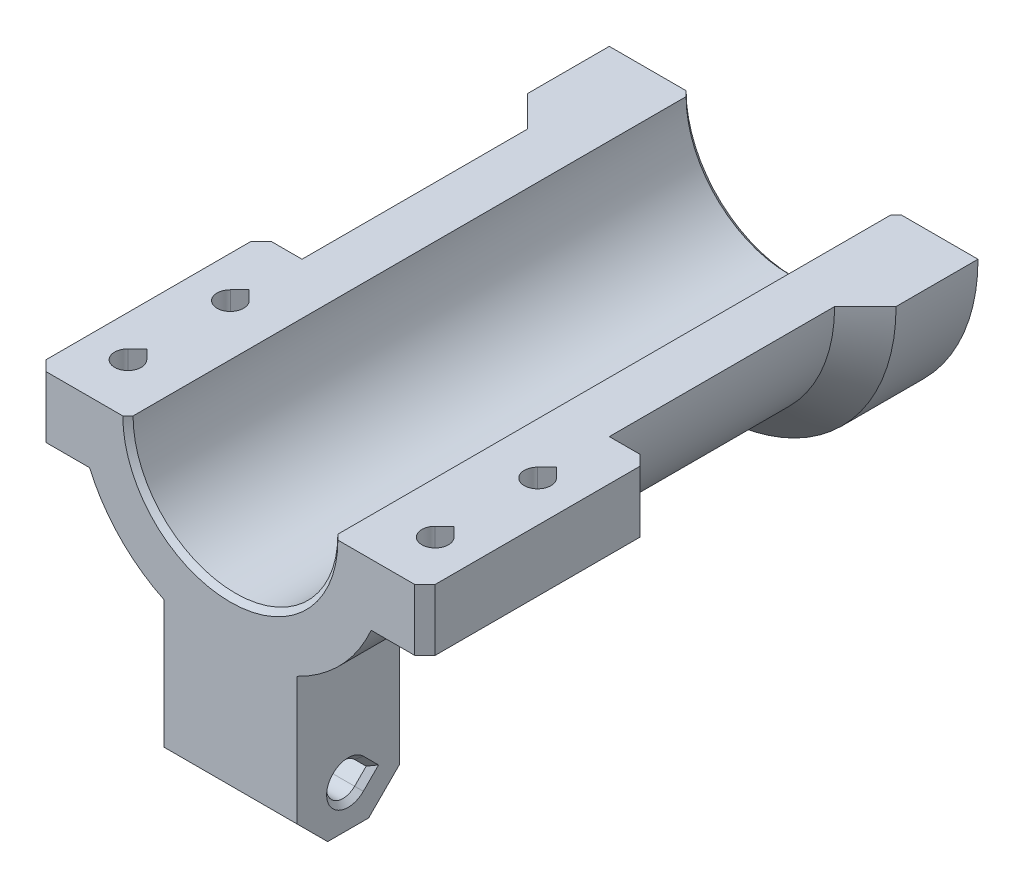
SolidWorks part; units mm, degrees
ref_plane "前视基准面" through (0, 0, 0) normal (0, 0, 1) x (1, 0, 0)
ref_plane "上视基准面" through (0, 0, 0) normal (0, 1, 0) x (1, 0, 0)
ref_plane "右视基准面" through (0, 0, 0) normal (1, 0, 0) x (0, 0, -1)
sketch "草图1" plane through (0, 0, 0) normal (0, 0, 1) x (1, 0, 0)
  line L0 (0, 34.6078) -> (0, -34.6078) construction
  line L1 (-30.8999, 0) -> (31.5242, 0) construction
  line L2 (-10, 0) -> (-19, 0)
  line L3 (-19, 0) -> (-19, -6)
  line L4 (-19, -6) -> (-13.7477, -6)
  line L5 (-15, 0) -> (-15, -3.9162) construction
  line L6 (-13.9, 0) -> (-13.9, -4.2934) construction
  line L7 (-13, 0) -> (-13, 2.8301) construction
  line L8 (-6.5, -13.5185) -> (-6.5, -29)
  line L9 (-6.5, -29) -> (6.5, -29)
  line L10 (-6.5, -25) -> (0, -25) construction
  line L11 (-6.5, -23.4) -> (0, -23.4) construction
  line L12 (-6.5, -22) -> (-10, -22) construction
  line L13 (6.5, -13.5185) -> (6.5, -29)
  line L14 (19, -6) -> (13.7477, -6)
  line L15 (19, 0) -> (19, -6)
  line L16 (10, 0) -> (19, 0)
  arc A0 (-10, 0) -> (10, 0) centre (0, 0) ccw
  arc A2 (-13.7477, -6) -> (-6.5, -13.5185) centre (0, 0) ccw
  arc A3 (13.7477, -6) -> (6.5, -13.5185) centre (0, 0) cw
  point P29 (0, -29)
  dimension "D1" = 10
  dimension "D2" = 38
  dimension "D3" = 9
  dimension "D5" = 1.1
  dimension "D4" = 13
  dimension "D7" = 5
  dimension "D6" = 2
  dimension "D8" = 25
  dimension "D9" = 1.6
  dimension "D10" = 3
  dimension "D11" = 4
  dimension "D12" = 30
  dimension "D13" = 6
extrude "凸台-拉伸1" add sketch "草图1" along normal blind 10
sketch "草图3" plane through (6.5, 0, 0) normal (1, 0, 0) x (0, 0, -1)
  line L0 (0, -25) -> (-5, -25) construction
  line L1 (0, -29) -> (0, -13.5185) construction
  line L2 (-10, -29) -> (0, -29) construction
  line L3 (-3.8686, -23.8686) -> (-2.7373, -25)
  line L4 (-3.8686, -26.1314) -> (-2.7373, -25)
  arc A0 (-3.8686, -23.8686) -> (-3.8686, -26.1314) centre (-5, -25) ccw
  dimension "D3" = 3.2
  dimension "D1" = 4
  dimension "D2" = 5
  dimension "D4" = 45
extrude "切除-拉伸1" cut sketch "草图3" against normal blind 54
sketch "草图4" plane through (0, 0, 0) normal (0, 1, 0) x (1, 0, 0)
  line L0 (10, -5) -> (-19, -5) construction
  line L1 (10, -10) -> (10, 0) construction
  line L3 (0, 0) -> (0, -23.0766) construction
  line L4 (-15, -5) -> (-15, -3.1615) construction
  line L5 (-15, -3.1615) -> (-15.9192, -4.0808)
  line L6 (-15, -3.1615) -> (-14.0808, -4.0808)
  line L7 (15, -5) -> (15, -3.1615) construction
  line L8 (15, -3.1615) -> (14.0808, -4.0808)
  line L9 (15, -3.1615) -> (15.9192, -4.0808)
  line L10 (-19, -10) -> (-19, 0) construction
  arc A0 (-15.9192, -4.0808) -> (-14.0808, -4.0808) centre (-15, -5) ccw
  arc A1 (15.9192, -4.0808) -> (14.0808, -4.0808) centre (15, -5) cw
  dimension "D1" = 30
  dimension "D2" = 2.6
  dimension "D3" = 45
extrude "切除-拉伸2" cut sketch "草图4" against normal blind 54
sketch "草图5" plane through (0, 0, 0) normal (0, 0, -1) x (-1, 0, 0)
  line L0 (10, 0) -> (15, 0)
  line L1 (-10, 0) -> (-15, 0)
  arc A0 (-10, 0) -> (10, 0) centre (0, 0) ccw construction
  arc A1 (-10, 0) -> (10, 0) centre (0, 0) ccw
  arc A2 (-15, 0) -> (15, 0) centre (0, 0) ccw
  arc A3 (6.5, -13.5185) -> (13.7477, -6) centre (0, 0) ccw construction
extrude "凸台-拉伸2" add sketch "草图5" along normal blind 45
chamfer "倒角1" distance 3 angle 45 2 edges at (0, -29, 0) (0, -29, 10)
sketch "草图8" plane through (0, 0, 0) normal (0, 0, -1) x (-1, 0, 0)
  line L0 (-15, 0) -> (-19, 0) construction
  line L1 (-19, 0) -> (-19, -6) construction
  line L2 (-19, -6) -> (-13.7477, -6) construction
  line L3 (13.7477, -6) -> (19, -6) construction
  line L4 (19, -6) -> (19, 0) construction
  line L5 (19, 0) -> (15, 0) construction
  line L6 (-15, 0) -> (-19, 0)
  line L7 (-19, 0) -> (-19, -6)
  line L8 (-19, -6) -> (-13.7477, -6)
  line L9 (13.7477, -6) -> (19, -6)
  line L10 (19, -6) -> (19, 0)
  line L11 (19, 0) -> (15, 0)
  arc A0 (-15, 0) -> (-13.7477, -6) centre (0, 0) ccw construction
  arc A1 (13.7477, -6) -> (15, 0) centre (0, 0) ccw construction
  arc A2 (-15, 0) -> (-13.7477, -6) centre (0, 0) ccw
  arc A3 (13.7477, -6) -> (15, 0) centre (0, 0) ccw
extrude "凸台-拉伸3" add sketch "草图8" along normal blind 12
sketch "草图9" plane through (0, 0, 0) normal (0, 1, 0) x (1, 0, 0)
  line L0 (0, 0) -> (0, 63.9683) construction
  line L1 (0, 5) -> (15, 5) construction
  line L2 (15, 5) -> (15, -5) construction
  line L3 (15, 5) -> (15, 6.8385) construction
  line L4 (15, 6.8385) -> (14.0808, 5.9192)
  line L5 (15, 6.8385) -> (15.9192, 5.9192)
  line L6 (-15, 5) -> (-15, 6.8385) construction
  line L7 (-15, 6.8385) -> (-15.9192, 5.9192)
  line L8 (-15, 6.8385) -> (-14.0808, 5.9192)
  arc A0 (14.0808, 5.9192) -> (15.9192, 5.9192) centre (15, 5) ccw
  arc A1 (-14.0808, 5.9192) -> (-15.9192, 5.9192) centre (-15, 5) cw
  dimension "D2" = 2.6
  dimension "D1" = 10
  dimension "D3" = 45
extrude "切除-拉伸4" cut sketch "草图9" against normal blind 12
sketch "草图10" plane through (0, 0, -45) normal (0, 0, -1) x (-1, 0, 0)
  line L0 (0, 0) -> (-30.1711, 0) construction
  line L1 (0, 0) -> (0, -34.5629) construction
  line L2 (-15, 0) -> (-18, 0)
  line L3 (15, 0) -> (18, 0)
  arc A0 (-15, 0) -> (15, 0) centre (0, 0) ccw construction
  arc A1 (-15, 0) -> (15, 0) centre (0, 0) ccw
  arc A2 (-18, 0) -> (18, 0) centre (0, 0) ccw
  arc M11 (-15, 0) -> (15, 0) centre (0, 0) ccw
  dimension "D1" = 3
extrude "凸台-拉伸4" add sketch "草图10" against normal blind 8 contours L2 A2 L3 M11 region at (0, -15.4025, -45)
chamfer "倒角7" distance 3 angle 45 1 edges at (0, -15, -37)
sketch "草图7" plane through (0, 0, -45) normal (0, 0, -1) x (-1, 0, 0)
  line L0 (0, 0) -> (0, -14) construction
  line L1 (0, 0) -> (-9.8995, -9.8995) construction
  circle A0 centre (0, 0) radius 14 construction
  circle A1 centre (-9.8995, -9.8995) radius 1.3
  circle A2 centre (9.8995, -9.8995) radius 1.3
  dimension "D1" = 28
  dimension "D3" = 2.6
  dimension "D2" = 45
extrude "切除-拉伸3" cut sketch "草图7" against normal blind 10
chamfer "倒角4" distance 1 angle 45 4 edges at (-19, -3, -12) (-19, -3, 10) (19, -3, -12) (19, -3, 10)
chamfer "倒角5" distance 0.5 angle 45 8 edges at (-6.5, -24.4343, 3.3029) (-6.5, -25.5657, 3.3029) (-6.5, -25, 6.6) (6.5, -24.4343, 3.3029) (6.5, -25.5657, 3.3029) (6.5, -25, 6.6) (0, -10, -45) (0, -10, 10)
chamfer "倒角6" distance 0.5 angle 45 4 edges at (-8.5995, -9.8995, -45) (-8.5995, -9.8995, -35) (8.5995, -9.8995, -45) (8.5995, -9.8995, -35)
